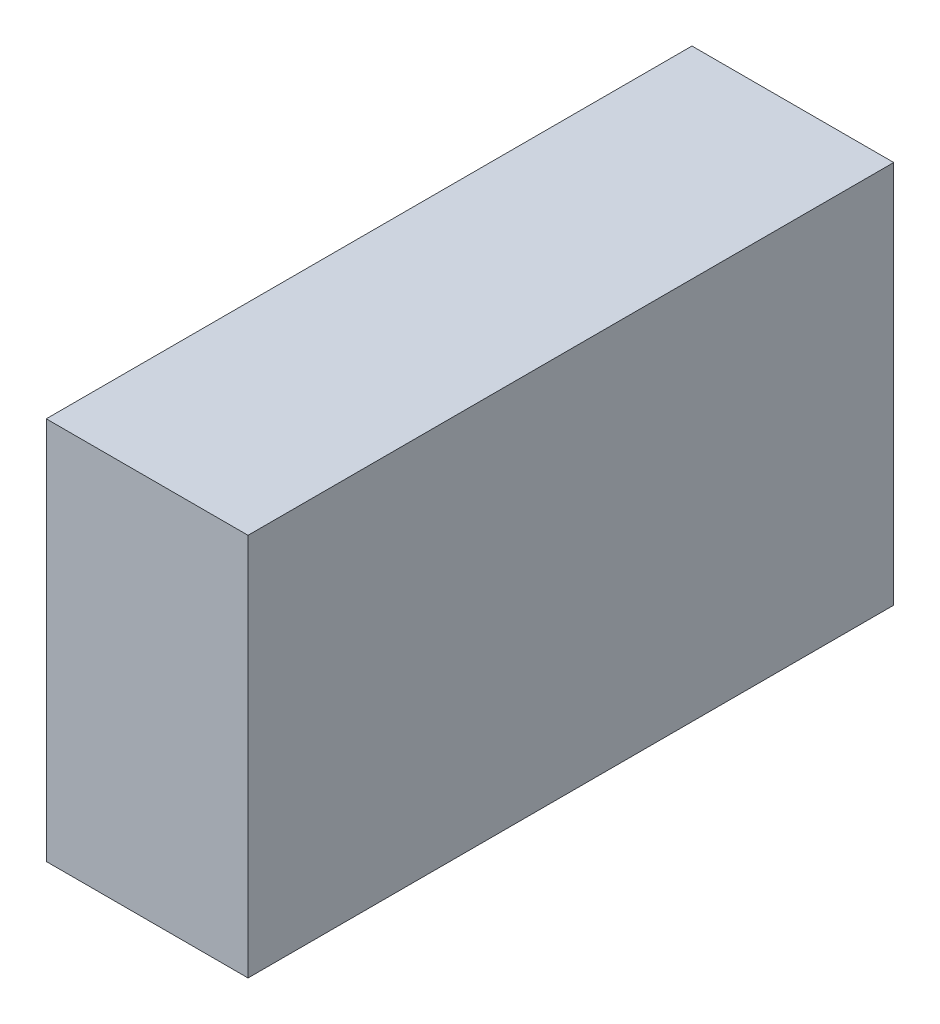
SolidWorks part; units mm, degrees
ref_plane "前视基准面" through (0, 0, 0) normal (0, 0, 1) x (1, 0, 0)
ref_plane "上视基准面" through (0, 0, 0) normal (0, 1, 0) x (1, 0, 0)
ref_plane "右视基准面" through (0, 0, 0) normal (1, 0, 0) x (0, 0, -1)
sketch "草图1" plane through (0, 0, 0) normal (0, 0, 1) x (1, 0, 0)
  line L1 (25, -47.5) -> (-25, -47.5)
  line L2 (25, -47.5) -> (25, 47.5)
  line L3 (25, 47.5) -> (-25, 47.5)
  line L4 (-25, -47.5) -> (-25, 47.5)
  line L5 (25, -47.5) -> (-25, 47.5) construction
  line L6 (25, 47.5) -> (-25, -47.5) construction
  point P0 (0, 0)
  dimension "D1" = 50
  dimension "D2" = 95
extrude "凸台-拉伸1" add sketch "草图1" along normal blind 160
